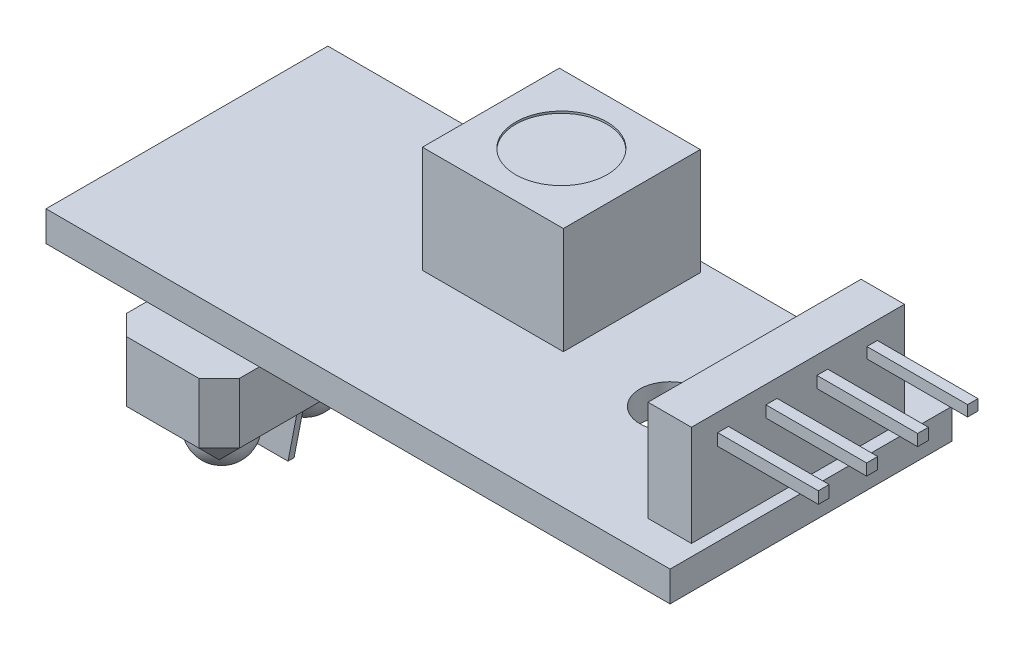
SolidWorks part; units mm, degrees
ref_plane "Front" through (0, 0, 0) normal (0, 0, 1) x (1, 0, 0)
ref_plane "Top" through (0, 0, 0) normal (0, 1, 0) x (1, 0, 0)
ref_plane "Right" through (0, 0, 0) normal (1, 0, 0) x (0, 0, -1)
sketch "草圖1" plane through (0, 0, 0) normal (0, 1, 0) x (1, 0, 0)
  line L1 (0, -7) -> (31, -7)
  line L2 (0, -7) -> (0, 7)
  line L3 (0, 7) -> (31, 7)
  line L4 (31, -7) -> (31, 7)
  dimension "D1" = 14
  dimension "D2" = 31
extrude "填料-伸長1" add sketch "草圖1" along normal blind 1.5
sketch "草圖2" plane through (0, 1.5, 0) normal (0, 1, 0) x (1, 0, 0)
  line L1 (12, 6.5) -> (19, 6.5)
  line L2 (12, 6.5) -> (12, -0.3)
  line L3 (12, -0.3) -> (19, -0.3)
  line L4 (19, 6.5) -> (19, -0.3)
  line L5 (31, 7) -> (0, 7) construction
  line L6 (0, 7) -> (0, -7) construction
  dimension "D1" = 6.8
  dimension "D2" = 7
  dimension "D3" = 0.5
  dimension "D4" = 12
extrude "填料-伸長2" add sketch "草圖2" along normal blind 5.3 separate body
sketch "草圖3" plane through (0, 1.5, 0) normal (0, 1, 0) x (1, 0, 0)
  line L1 (28.2749, 5.2139) -> (30.4297, 5.2139)
  line L2 (28.2749, 5.2139) -> (28.2749, -5.3678)
  line L3 (28.2749, -5.3678) -> (30.4297, -5.3678)
  line L4 (30.4297, 5.2139) -> (30.4297, -5.3678)
extrude "填料-伸長3" add sketch "草圖3" along normal blind 5 separate body
sketch "草圖5" plane through (30.4297, 0, 0) normal (1, 0, 0) x (0, 0, -1)
  line L1 (-4.063, 5.6149) -> (-3.5286, 5.6149)
  line L2 (-4.063, 5.6149) -> (-4.063, 5.0288)
  line L3 (-4.063, 5.0288) -> (-3.5286, 5.0288)
  line L4 (-3.5286, 5.6149) -> (-3.5286, 5.0288)
  line L5 (-1.6668, 5.6149) -> (-1.1152, 5.6149)
  line L6 (-1.6668, 5.6149) -> (-1.6668, 5.046)
  line L7 (-1.6668, 5.046) -> (-1.1152, 5.046)
  line L8 (-1.1152, 5.6149) -> (-1.1152, 5.046)
  line L9 (0.8673, 5.6149) -> (1.4017, 5.6149)
  line L10 (0.8673, 5.6149) -> (0.8673, 5.046)
  line L11 (0.8673, 5.046) -> (1.4017, 5.046)
  line L12 (1.4017, 5.6149) -> (1.4017, 5.046)
  line L13 (3.3496, 5.6149) -> (3.8668, 5.6149)
  line L14 (3.3496, 5.6149) -> (3.3496, 5.0805)
  line L15 (3.3496, 5.0805) -> (3.8668, 5.0805)
  line L16 (3.8668, 5.6149) -> (3.8668, 5.0805)
extrude "填料-伸長4" add sketch "草圖5" along normal blind 5
sketch "草圖6" plane through (0, 0, 0) normal (0, -1, 0) x (1, 0, 0)
  line L0 (0, -7) -> (0, 7) construction
  line L1 (1, -5) -> (6.6, -5)
  line L2 (1, -5) -> (1, 5)
  line L3 (1, 5) -> (6.6, 5)
  line L4 (6.6, -5) -> (6.6, 5)
  line L5 (31, -7) -> (0, -7) construction
  line L6 (0, 7) -> (31, 7) construction
  dimension "D1" = 1
  dimension "D2" = 2
  dimension "D3" = 2
  dimension "D4" = 5.6
extrude "填料-伸長5" add sketch "草圖6" along normal blind 4 from offset 4 separate body
sketch "草圖7" plane through (0, 0, 0) normal (0, -1, 0) x (1, 0, 0)
  line L1 (2.1643, 2.8635) -> (2.7643, 2.8635)
  line L2 (2.1643, 2.8635) -> (2.1643, 2.2635)
  line L3 (2.1643, 2.2635) -> (2.7643, 2.2635)
  line L4 (2.7643, 2.8635) -> (2.7643, 2.2635)
  line L5 (4.7968, 2.905) -> (5.3968, 2.905)
  line L6 (4.7968, 2.905) -> (4.7968, 2.305)
  line L7 (4.7968, 2.305) -> (5.3968, 2.305)
  line L8 (5.3968, 2.905) -> (5.3968, 2.305)
  line L9 (2.2887, -2.1527) -> (2.8887, -2.1527)
  line L10 (2.2887, -2.1527) -> (2.2887, -2.7527)
  line L11 (2.2887, -2.7527) -> (2.8887, -2.7527)
  line L12 (2.8887, -2.1527) -> (2.8887, -2.7527)
  line L13 (4.8175, -2.1112) -> (5.4175, -2.1112)
  line L14 (4.8175, -2.1112) -> (4.8175, -2.7112)
  line L15 (4.8175, -2.7112) -> (5.4175, -2.7112)
  line L16 (5.4175, -2.1112) -> (5.4175, -2.7112)
  dimension "D1" = 0.6
  dimension "D2" = 0.6
  dimension "D3" = 0.6
  dimension "D4" = 0.6
  dimension "D5" = 0.6
  dimension "D6" = 0.6
  dimension "D7" = 0.6
  dimension "D8" = 0.6
extrude "填料-伸長6" add sketch "草圖7" along normal up to next separate body
chamfer "導角1" distance 1 angle 45 6 edges at (3.8, -8, 5) (1, -6, 5) (1, -8, 0) (3.8, -8, -5) (6.6, -8, 0) (6.6, -6, 5)
sketch "草圖8" plane through (0, 1.5, 0) normal (0, 1, 0) x (1, 0, 0)
  line L0 (0, 0) -> (24, 0) construction
  circle A0 centre (24, 0) radius 1.5
  dimension "D1" = 3
  dimension "D2" = 24
extrude "除料-伸長1" cut sketch "草圖8" against normal blind 3
sketch "草圖9" plane through (0, -8, 0) normal (0, -1, 0) x (1, 0, 0)
  line L1 (2, 0.15) -> (5.6, 0.15)
  line L2 (2, 0.15) -> (2, -0.15)
  line L3 (2, -0.15) -> (5.6, -0.15)
  line L4 (5.6, 0.15) -> (5.6, -0.15)
  line L6 (0, 0) -> (2, 0) construction
  line L7 (2, 4) -> (2, -4) construction
  dimension "D1" = 0.3
  dimension "D2" = 3.6
extrude "填料-伸長7" add sketch "草圖9" along normal blind 2.2
chamfer "導角2" distance 2.2 angle 11 2 edges at (5.6, -10.2, 0) (2, -10.2, 0) first distance on face at (5.6, -9.1, 0) first distance on face at (2, -9.1, 0)
ref_plane "平面1" through (3.8, 0, 0) normal (-1, 0, 0) x (0, 0, 1)
sketch "草圖10" plane through (3.8, 0, 0) normal (-1, 0, 0) x (0, 0, 1)
  line L0 (-2.075, -8) -> (-2.075, -9.8)
  line L3 (-0.15, -8) -> (-4, -8) construction
  line L4 (-3.475, -8.4) -> (-3.475, -8)
  line L5 (-3.475, -8) -> (-2.075, -8)
  arc A0 (-2.075, -9.8) -> (-3.475, -8.4) centre (-2.075, -8.4) cw
  dimension "D1" = 1.8
  dimension "D2" = 1.4
revolve "旋轉1" add sketch "草圖10" angle 360 about L0
sketch "草圖11" plane through (3.8, 0, 0) normal (-1, 0, 0) x (0, 0, 1)
  line L0 (2.075, -8) -> (2.075, -9.8)
  line L3 (3.475, -8.4) -> (3.475, -8)
  line L4 (4, -8) -> (0.15, -8) construction
  line L5 (3.475, -8) -> (2.075, -8)
  arc A0 (2.075, -9.8) -> (3.475, -8.4) centre (2.075, -8.4) ccw
  dimension "D1" = 1.8
  dimension "D2" = 1.4
revolve "旋轉2" add sketch "草圖11" angle 360 about L0
sketch "草圖12" plane through (0, 6.8, 0) normal (0, 1, 0) x (1, 0, 0)
  circle A0 centre (15.5, 3.1) radius 2.2703
extrude "除料-伸長2" cut sketch "草圖12" against normal blind 0.1
